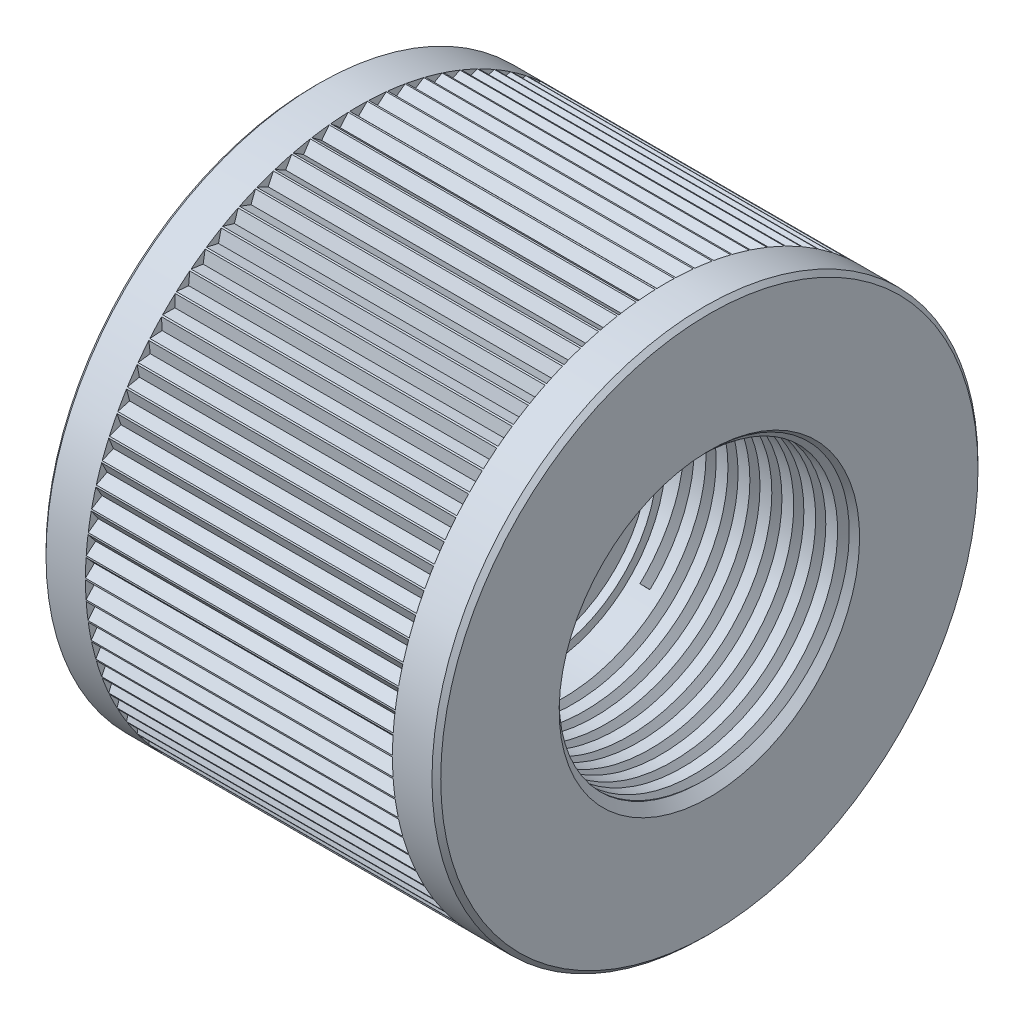
SolidWorks part; units mm, degrees
ref_plane "Front Plane" through (0, 0, 0) normal (0, 0, 1) x (1, 0, 0)
ref_plane "Top Plane" through (0, 0, 0) normal (0, 1, 0) x (1, 0, 0)
ref_plane "Right Plane" through (0, 0, 0) normal (1, 0, 0) x (0, 0, -1)
sketch "Sketch1" plane through (0, 0, 0) normal (0, 0, 1) x (1, 0, 0)
  line L0 (0, 0) -> (9, 0) construction
  line L1 (0, 6.225) -> (9, 6.225)
  line L2 (9, 6.225) -> (9, 3.225)
  line L3 (9, 3.225) -> (0, 3.225)
  line L4 (0, 3.225) -> (0, 6.225)
  dimension "D1" = 9
  dimension "D2" = 6.225
  dimension "D4" = 3.225
revolve "Revolve1" add sketch "Sketch1" angle 360 about L0
chamfer "Chamfer1" distance 0.1 angle 45 2 edges at (0, 0, 6.225) (9, 0, 6.225)
ref_plane "Plane1" through (1, 0, 0) normal (1, 0, 0) x (0, 0, -1)
sketch "Sketch2" plane through (1, 0, 0) normal (1, 0, 0) x (0, 0, -1)
  line L0 (0, 0) -> (0, 6.2259) construction
  line L1 (0.2, 6.2227) -> (0, 6.0259)
  line L2 (0, 6.0259) -> (-0.2, 6.2227)
  arc A0 (0.2, 6.2227) -> (-0.2, 6.2227) centre (0, 0) ccw
  dimension "D1" = 0.4
  dimension "D2" = 0.2
extrude "Cut-Extrude1" cut sketch "Sketch2" along normal blind 7
pattern_circular "CirPattern1" count 90 over 360 about axis through (8.9, 0, 0) along (-1, 0, 0) of "Cut-Extrude1"
chamfer "Chamfer2" distance 0.2 angle 45 1 edges at (9, 0, 3.225)
ref_plane "Plane2" through (5, 0, 0) normal (1, 0, 0) x (0, 0, -1)
sketch "Sketch3" plane through (5, 0, 0) normal (1, 0, 0) x (0, 0, -1)
  circle A0 centre (0, 0) radius 2.9862
extrude "Boss-Extrude1" add sketch "Sketch3" against normal blind 5 separate body
sketch "Sketch4" plane through (5, 0, 0) normal (1, 0, 0) x (0, 0, -1)
  circle A0 centre (0, 0) radius 2.806
  circle A1 centre (0, 0) radius 2.612
extrude "Boss-Extrude2" add sketch "Sketch4" along normal blind 0.2
sketch "Sketch5" plane through (5, 0, 0) normal (1, 0, 0) x (0, 0, -1)
  circle A0 centre (0, 0) radius 0.5
  dimension "D1" = 1
extrude "Cut-Extrude2" cut sketch "Sketch5" against normal blind 1
sketch "Sketch6" plane through (4, 0, 0) normal (1, 0, 0) x (0, 0, -1)
  line L0 (0, 0.4187) -> (0, 0.4627) construction
  line L1 (0.1136, 0.4485) -> (0.1136, 0.403)
  line L2 (-0.1136, 0.4485) -> (-0.1136, 0.403)
  line L3 (-0.1136, -0.403) -> (-0.1136, -0.4485)
  line L4 (0.1136, -0.403) -> (0.1136, -0.4485)
  arc A0 (-0.1136, 0.4485) -> (-0.1136, -0.4485) centre (0, 0) ccw
  arc A1 (-0.1136, 0.403) -> (-0.1136, -0.403) centre (0, 0) ccw
  arc A2 (0.1136, -0.403) -> (0.1136, 0.403) centre (0, 0) ccw
  arc A3 (0.1136, -0.4485) -> (0.1136, 0.4485) centre (0, 0) ccw
extrude "Boss-Extrude3" add sketch "Sketch6" along normal blind 1
sketch "Sketch7" plane through (9, 0, 0) normal (1, 0, 0) x (0, 0, -1)
  circle A0 centre (0, 0) radius 3.425
  circle A1 centre (0, 0) radius 3.425 construction
curve "Helix/Spiral1" pitch 0.5 height 3.75 radius 3.425 centre (9, 0, 0) axis (-1, 0, 0) start towards (0, 0.7071, 0.7071)
ref_plane "Plane3" through (9, 2.4218, 2.4218) normal (-0.0232, 0.7069, -0.7069) x (-0.9997, -0.0164, 0.0164)
sketch "Sketch8" plane through (9, 2.4218, 2.4218) normal (-0.0232, 0.7069, -0.7069) x (-0.9997, -0.0164, 0.0164)
  line L1 (0, 0) -> (-0.2, -0.3464)
  line L2 (-0.2, -0.3464) -> (0.2, -0.3464)
  line L3 (0.2, -0.3464) -> (0, 0)
  circle A0 centre (0, -0.2309) radius 0.1155 construction
  ellipse E0 centre (0, -3.425) end of major axis (0, -6.85) minor radius 0.0796 construction
  dimension "D1" = 0.4
sweep "Cut-Sweep2" cut profiles "Sketch8" path "Helix/Spiral1" align with end faces yes
sketch "Sketch9" plane through (4, 0, 0) normal (1, 0, 0) x (0, 0, -1)
  circle A0 centre (0, 0) radius 0.3851
extrude "Cut-Extrude3" cut sketch "Sketch9" against normal through all
